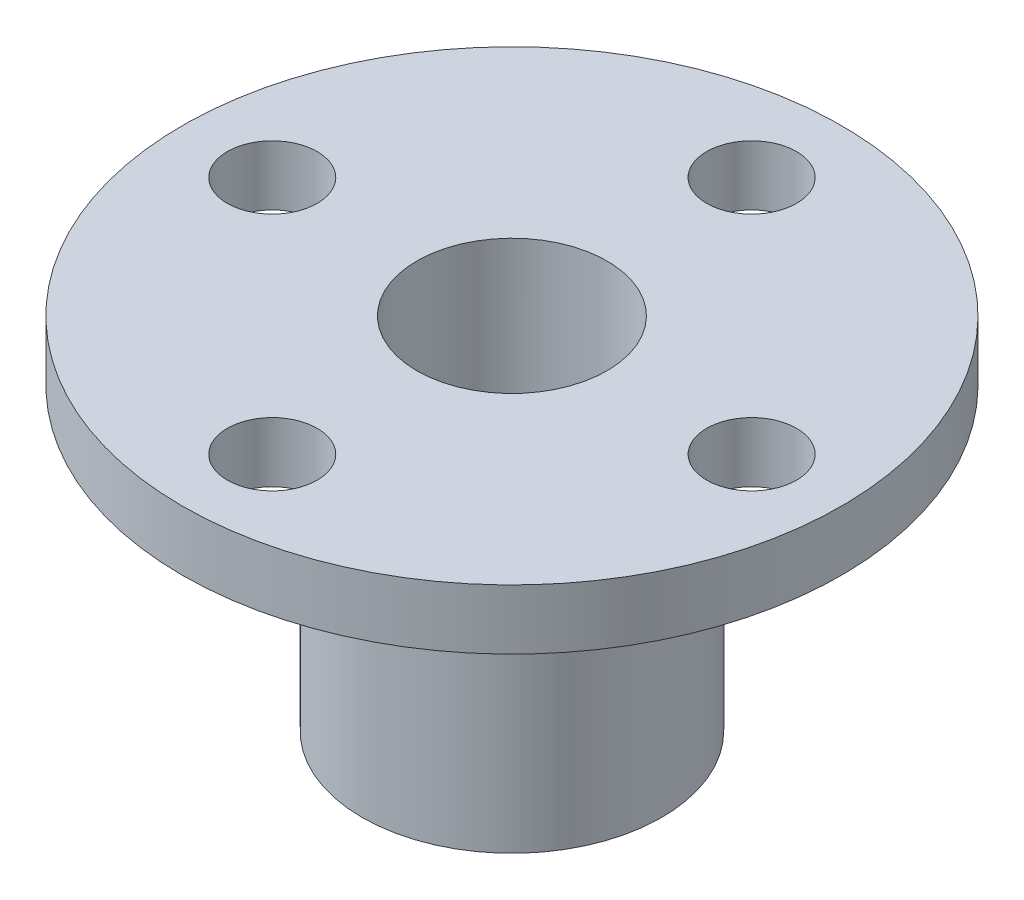
SolidWorks part; units mm, degrees
ref_plane "Front Plane" through (0, 0, 0) normal (0, 0, 1) x (1, 0, 0)
ref_plane "Top Plane" through (0, 0, 0) normal (0, 1, 0) x (1, 0, 0)
ref_plane "Right Plane" through (0, 0, 0) normal (1, 0, 0) x (0, 0, -1)
sketch "Sketch1" plane through (0, 0, 0) normal (0, 1, 0) x (1, 0, 0)
  circle A0 centre (0, 0) radius 3.175
  circle A1 centre (0, 0) radius 5
  dimension "D1" = 6.35
  dimension "D2" = 10
extrude "Boss-Extrude1" add sketch "Sketch1" along normal blind 12
sketch "Sketch2" plane through (0, 12, 0) normal (0, 1, 0) x (1, 0, 0)
  circle A0 centre (0, 0) radius 11
  circle A1 centre (0, 0) radius 3.175 construction
  circle A2 centre (0, 0) radius 3.175
  dimension "D1" = 22
extrude "Boss-Extrude2" add sketch "Sketch2" against normal blind 2
sketch "Sketch3" plane through (0, 12, 0) normal (0, 1, 0) x (1, 0, 0)
  line L0 (0, 11) -> (0, -11) construction
  circle A0 centre (0, 0) radius 8 construction
  circle A1 centre (0, 8) radius 1.5
  circle A2 centre (0, 0) radius 11 construction
  circle A3 centre (8, 0) radius 1.5
  circle A4 centre (0, -8) radius 1.5
  circle A5 centre (-8, 0) radius 1.5
  point P19 (0, 0)
  dimension "D1" = 16
  dimension "D2" = 3
  dimension "D3" = 4
extrude "Cut-Extrude1" cut sketch "Sketch3" against normal through all
ref_axis "Axis1" through (0, -0.6, 0) along (0, 1, 0)
ref_plane "Plane1" through (0, 0, 0) normal (0.7071, 0, 0.7071) x (0, 1, 0)
sketch "Sketch4" plane through (0, 0, 0) normal (0.7071, 0, 0.7071) x (0, 1, 0)
  line L1 (0, 0) -> (2, 0)
  circle A0 centre (3.5, 0) radius 1.5
  dimension "D1" = 3
  dimension "D2" = 2
extrude "Cut-Extrude2" cut sketch "Sketch4" against normal through all contours A0 region at (0, 3.5, 0)
equation "\"plate_thickness\"= 2mm"
equation "\"D1@Boss-Extrude2\"=\"plate_thickness\""
equation "\"set screw diam\"= 3mm"
equation "\"D1@Sketch4\"=\"set screw diam\""
equation "\"set screw offset from end\"= 2mm"
equation "\"D2@Sketch4\"=\"set screw offset from end\""
